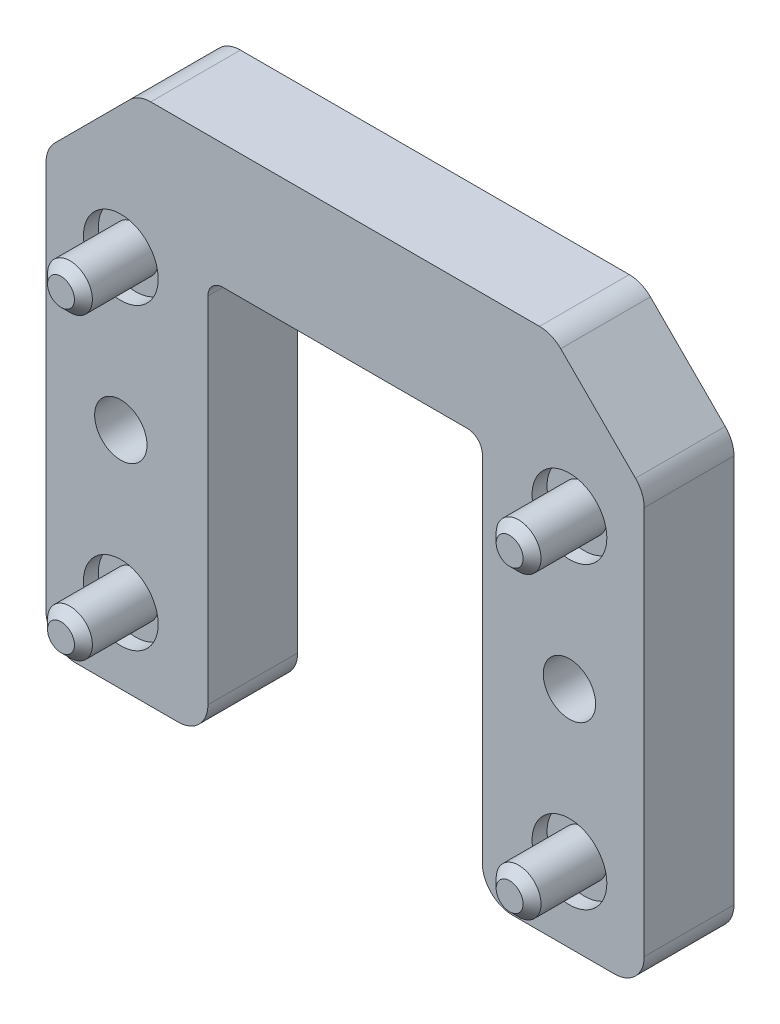
SolidWorks part; units mm, degrees
ref_plane "Přední rovina" through (0, 0, 0) normal (0, 0, 1) x (1, 0, 0)
ref_plane "Horní rovina" through (0, 0, 0) normal (0, 1, 0) x (1, 0, 0)
ref_plane "Pravá rovina" through (0, 0, 0) normal (1, 0, 0) x (0, 0, -1)
sketch "Skica1" plane through (0, 0, 0) normal (0, 0, 1) x (1, 0, 0)
  line L1 (-10.175, -12.675) -> (10.175, -12.675) construction
  line L2 (-10.175, -12.675) -> (-10.175, 12.675) construction
  line L3 (-10.175, 12.675) -> (10.175, 12.675) construction
  line L4 (10.175, -12.675) -> (10.175, 12.675) construction
  line L5 (-10.175, -12.675) -> (10.175, 12.675) construction
  line L6 (-10.175, 12.675) -> (10.175, -12.675) construction
  point P0 (0, 0)
  dimension "D1" = 20.35
  dimension "D2" = 25.35
sketch "Skica2" plane through (0, 0, 0) normal (0, 0, 1) x (1, 0, 0)
  line L0 (-10.175, 12.675) -> (10.175, 12.675) construction
  line L2 (-20, 13) -> (-20, -15)
  line L3 (-20, -15) -> (20, -15)
  line L4 (20, 13) -> (20, -15)
  line L5 (-9.175, 11.675) -> (9.175, 11.675)
  line L6 (-9.175, 11.675) -> (-9.175, -11.675)
  line L7 (-9.175, -11.675) -> (9.175, -11.675)
  line L8 (9.175, 11.675) -> (9.175, -11.675)
  line L9 (-10.175, -12.675) -> (-10.175, 12.675) construction
  line L10 (-15, 0) -> (15, 0) construction
  line L11 (-19.4142, 14.4142) -> (-13.8284, 20)
  line L12 (-15, -10) -> (15, -10) construction
  line L13 (-15, -10) -> (-15, 10) construction
  line L14 (-15, 10) -> (15, 10) construction
  line L15 (15, -10) -> (15, 10) construction
  line L16 (-15, -10) -> (15, 10) construction
  line L17 (-15, 10) -> (15, -10) construction
  line L18 (-13.8284, 20) -> (13.8284, 20)
  line L19 (13.8284, 20) -> (19.4142, 14.4142)
  circle A0 centre (-15, 0) radius 2.85 construction
  circle A1 centre (-15, 0) radius 1.75
  circle A2 centre (15, 0) radius 1.75
  circle A3 centre (-15, 10) radius 1.5
  circle A4 centre (15, 10) radius 1.5
  circle A5 centre (15, -10) radius 1.5
  circle A6 centre (-15, -10) radius 1.5
  arc A7 (20, 13) -> (19.4142, 14.4142) centre (18, 13) ccw
  arc A8 (-19.4142, 14.4142) -> (-20, 13) centre (-18, 13) ccw
  point P12 (0, 12.675)
  point P13 (0, 11.675)
  point P16 (-10.175, 0)
  point P17 (-9.175, 0)
  point P23 (0, 0)
  point P33 (0, 0)
  point P34 (20, 13.8284)
  point P41 (0, 20)
  point P45 (0, -11.675)
  point P46 (0, -15)
  dimension "D1" = 5.7
  dimension "D7" = 3.5
  dimension "D10" = 3
  dimension "D5" = 2
  dimension "D2" = 1
  dimension "D3" = 1
  dimension "D6" = 15
  dimension "D8" = 30
  dimension "D9" = 30
  dimension "D11" = 20
  dimension "D12" = 40
  dimension "D13" = 35
  dimension "D14" = 45
  dimension "D15" = 28
extrude "Přidat vysunutím1" add sketch "Skica2" against normal blind 6 contours L4 L2 L3 A6 A5 A4 A3 A2 A1 L5 L8 L7 L6 | A3 | A6 | A5 | A4 | L19 L18 L11 region at (-19.3567, 13.562, 0) region at (-15, 10, 0) region at (15, 10, 0) region at (15, -10, 0) region at (-15, -10, 0)
sketch "Skica3" plane through (0, 0, 0) normal (0, 0, 1) x (1, 0, 0)
  line L0 (-10.175, 12.675) -> (10.175, 12.675) construction
  line L1 (-10.375, -12.875) -> (10.375, -12.875)
  line L2 (-10.375, -12.875) -> (-10.375, 12.875)
  line L3 (-10.375, 12.875) -> (10.375, 12.875)
  line L4 (10.375, -12.875) -> (10.375, 12.875)
  line L5 (-10.375, -12.875) -> (10.375, 12.875) construction
  line L6 (-10.375, 12.875) -> (10.375, -12.875) construction
  line L7 (-10.175, -12.675) -> (-10.175, 12.675) construction
  point P0 (0, 0)
  dimension "D1" = 0.2
  dimension "D2" = 0.2
extrude "Přidat vysunutím2" add sketch "Skica2<3>" along normal blind 4 contours A6 | A5 | A4 | A3 region at (15, 10, 0) region at (15, -10, 0) region at (-15, -10, 0)
sketch "Skica2<3>" plane through (0, 0, 0) normal (0, 0, 1) x (1, 0, 0) same geometry as "Skica2"
sketch "Skica4" plane through (0, 0, 0) normal (0, 0, 1) x (1, 0, 0)
  line L1 (-9.175, -11.675) -> (9.175, -11.675)
  line L2 (-9.175, -11.675) -> (-9.175, -15)
  line L3 (-9.175, -15) -> (9.175, -15)
  line L4 (9.175, -11.675) -> (9.175, -15)
  line L5 (-20, -15) -> (20, -15) construction
  line L6 (-9.175, 11.675) -> (-9.175, -11.675) construction
  line L8 (-9.175, -11.675) -> (9.175, -11.675) construction
  point P4 (0, -11.675)
extrude "Odebrat vysunutím2" cut sketch "Skica4" against normal through all contours L2 L3 L4 L1
sketch "Skica5" plane through (0, 0, 0) normal (0, 0, 1) x (1, 0, 0)
  circle A0 centre (15, 10) radius 1.5 construction
  circle A1 centre (15, -10) radius 1.5 construction
  circle A2 centre (-15, -10) radius 1.5 construction
  circle A3 centre (-15, 10) radius 1.5 construction
  circle A4 centre (15, 10) radius 1.5
  circle A5 centre (15, -10) radius 1.5
  circle A6 centre (-15, -10) radius 1.5
  circle A7 centre (-15, 10) radius 1.5
  circle A8 centre (-15, 10) radius 2.5
  circle A9 centre (-15, -10) radius 2.5
  circle A10 centre (15, -10) radius 2.5
  circle A11 centre (15, 10) radius 2.5
  dimension "D1" = 1
extrude "Odebrat vysunutím3" cut sketch "Skica5" against normal blind 1
chamfer "Zkosení1" distance 0.6 angle 45 4 edges at (-13.5, -10, 4) (16.5, -10, 4) (16.5, 10, 4) (-13.5, 10, 4)
fillet "Zaoblit1" radius 2 6 edges at (20, -15, -3) (-20, -15, -3) (9.175, -15, -3) (-9.175, -15, -3) (13.8284, 20, -3) (-13.8284, 20, -3)
fillet "Zaoblit2" radius 1 2 edges at (9.175, 11.675, -3) (-9.175, 11.675, -3)
